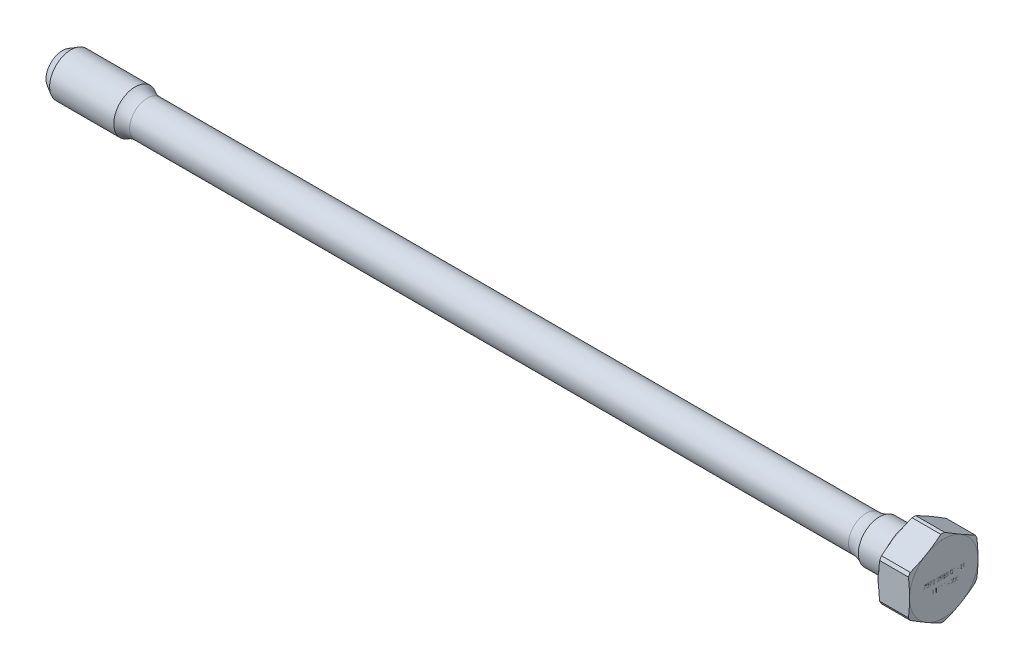
SolidWorks part; units mm, degrees
material "4340 H/T-Y"
ref_plane "Front Plane" through (0, 0, 0) normal (0, 0, 1) x (1, 0, 0)
ref_plane "Top Plane" through (0, 0, 0) normal (0, 1, 0) x (1, 0, 0)
ref_plane "Right Plane" through (0, 0, 0) normal (1, 0, 0) x (0, 0, -1)
sketch "Sketch1" plane through (0, 0, 0) normal (0, 0, 1) x (1, 0, 0)
  line L0 (8, 0) -> (6.7983, 2)
  line L1 (6.7983, 2) -> (3.4641, 2)
  line L2 (3.4641, 2) -> (0, 4)
  line L3 (0, 4) -> (0, 7.6906)
  line L4 (0, 7.6906) -> (4, 10)
  line L5 (4, 10) -> (34, 10)
  line L6 (8, 0) -> (412, 0)
  line L7 (39.6513, 8.25) -> (375.7064, 8.25)
  line L9 (382, 9.95) -> (395, 9.95)
  line L10 (397, 11.95) -> (397, 15.75)
  line L11 (397, 15.75) -> (397.5, 15.75)
  line L12 (397.5, 15.75) -> (397.5, 16)
  line L13 (397.5, 16) -> (398.0359, 18)
  line L14 (398.0359, 18) -> (411.4641, 18)
  line L15 (411.4641, 18) -> (412, 16)
  line L16 (412, 16) -> (412, 0)
  line L17 (412, 0) -> (8, 0) construction
  arc A0 (39.6513, 8.25) -> (34, 10) centre (39.6513, 18.25) cw
  arc A1 (375.7064, 8.25) -> (382, 9.95) centre (375.7064, 20.75) ccw
  arc A2 (397, 11.95) -> (395, 9.95) centre (395, 11.95) cw
  dimension "D13" = 10
  dimension "D16" = 12.5
  dimension "D23" = 2
  dimension "D1" = 412
  dimension "D2" = 0.5
  dimension "D3" = 397
  dimension "D4" = 4
  dimension "D5" = 8
  dimension "D6" = 59
  dimension "D7" = 30
  dimension "D8" = 8
  dimension "D9" = 4
  dimension "D10" = 30
  dimension "D11" = 20
  dimension "D12" = 16.5
  dimension "D14" = 34
  dimension "D15" = 19.9
  dimension "D17" = 382
  dimension "D18" = 31.5
  dimension "D19" = 36
  dimension "D20" = 32
  dimension "D21" = 15
  dimension "D22" = 75
revolve "Revolve1" add sketch "Sketch1" angle 360 about L17
cosmetic thread "Cosmetic Thread1" parameters "D2"=18
sketch "Sketch3" plane through (412, 0, 0) normal (1, 0, 0) x (0, 0, -1)
  line L1 (0, 18.4752) -> (-16, 9.2376)
  line L2 (-16, 9.2376) -> (-16, -9.2376)
  line L3 (-16, -9.2376) -> (0, -18.4752)
  line L4 (0, -18.4752) -> (16, -9.2376)
  line L5 (16, -9.2376) -> (16, 9.2376)
  line L6 (16, 9.2376) -> (0, 18.4752)
  circle A0 centre (0, 0) radius 16 construction
extrude "Cut-Extrude-Thin1" cut sketch "Sketch3" against normal up to surface (14.5 mm away) thin contours L2 L3 L4 L5 L6 L1 up to face at (397.5, 15.75, 0) thin type one direction wall 10
sketch "Sketch4" plane through (412, 0, 0) normal (-1, 0, 0) x (0, 0, -1)
  line L0 (-13.7374, 0) -> (13.8626, 0) construction
  line L1 (0, 17.7946) -> (0, -13.217) construction
  text T0 "7372 2988 01 - H\r\n 11111 - XX" font "Century Gothic" height 1.8
extrude "Cut-Extrude1" cut sketch "Sketch4" along normal blind 0.01
